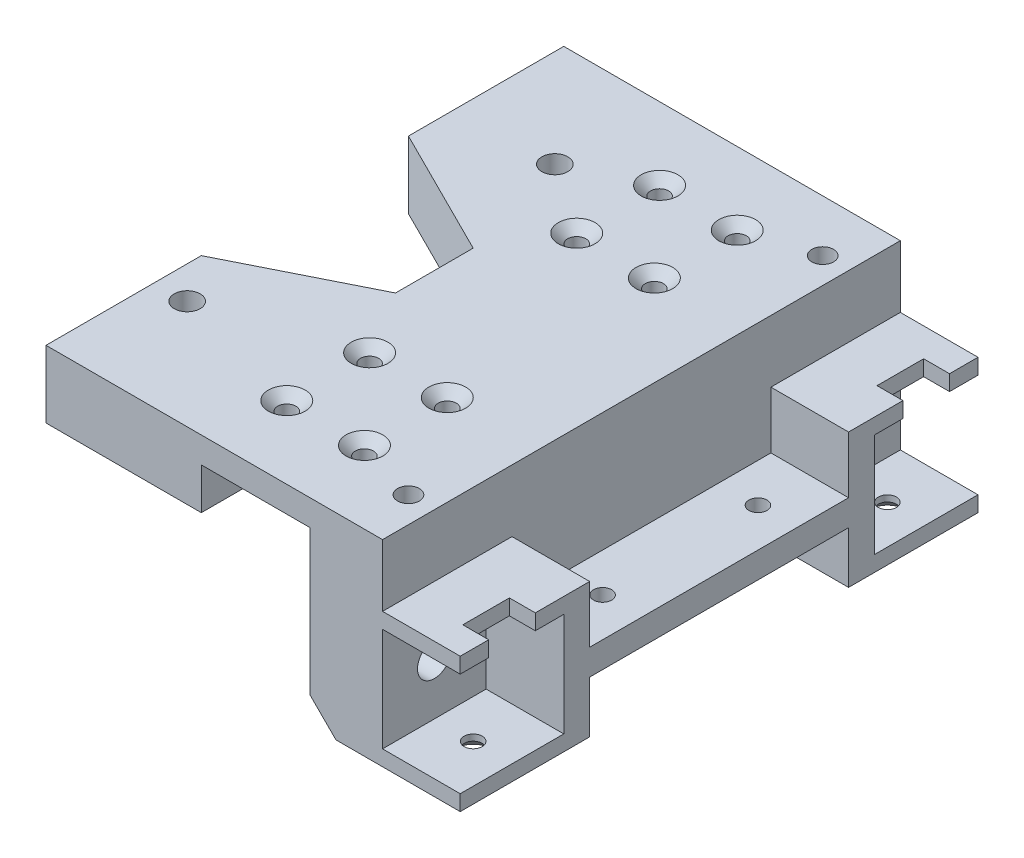
SolidWorks part; units mm, degrees
ref_plane "Front Plane" through (0, 0, 0) normal (0, 0, 1) x (1, 0, 0)
ref_plane "Top Plane" through (0, 0, 0) normal (0, 1, 0) x (1, 0, 0)
ref_plane "Right Plane" through (0, 0, 0) normal (1, 0, 0) x (0, 0, -1)
sketch "Sketch1" plane through (0, 0, 0) normal (0, 1, 0) x (1, 0, 0)
  line L0 (0, 50) -> (0, -50) construction
  line L1 (-10, 50) -> (10, 50)
  line L2 (-10, 50) -> (-10, -50)
  line L3 (-10, -50) -> (10, -50)
  line L4 (10, 50) -> (10, -50) construction
  line L5 (-10, 50) -> (10, -50) construction
  line L6 (-10, -50) -> (10, 50) construction
  line L7 (-7.5, 36) -> (7.5, 36) construction
  line L8 (-7.5, 36) -> (7.5, 20) construction
  line L9 (-10, 0) -> (10, 0) construction
  line L10 (-7.5, -36) -> (7.5, -20) construction
  line L11 (-7.5, -36) -> (7.5, -36) construction
  line L12 (-7.5, 20) -> (7.5, 20) construction
  line L13 (10, 50) -> (11, 50)
  line L14 (11, 50) -> (11, -50)
  line L15 (11, -50) -> (10, -50)
  circle A0 centre (-7.5, 36) radius 1.75
  circle A1 centre (7.5, 36) radius 1.75
  circle A2 centre (-7.5, 20) radius 1.75
  circle A3 centre (7.5, 20) radius 1.75
  circle A4 centre (7.5, -20) radius 1.75
  circle A5 centre (-7.5, -20) radius 1.75
  circle A6 centre (7.5, -36) radius 1.75
  circle A7 centre (-7.5, -36) radius 1.75
  point P0 (0, 0)
  point P16 (0, 36)
  dimension "D2" = 3.5
  dimension "D1" = 20
  dimension "D3" = 15
  dimension "D4" = 16
  dimension "D5" = 100
  dimension "D6" = 20
  dimension "D7" = 1
extrude "Boss-Extrude1" add sketch "Sketch1" along normal blind 5
sketch "Sketch2" plane through (11, 0, 0) normal (1, 0, 0) x (0, 0, -1)
  line L1 (-50, 5) -> (50, 5)
  line L2 (-50, 5) -> (-50, -33)
  line L3 (-50, -33) -> (50, -33)
  line L5 (50, 5) -> (50, -33)
  line L6 (50, 5) -> (50, 0) construction
  line L7 (-50, 5) -> (-50, 0) construction
  line L8 (-50, 5) -> (50, 5) construction
  dimension "D1" = 38
extrude "Boss-Extrude2" add sketch "Sketch2" along normal blind 14
sketch "Sketch3" plane through (25, 0, 0) normal (1, 0, 0) x (0, 0, -1)
  line L0 (0, 5) -> (0, -33) construction
  line L1 (-25, -18) -> (25, -18)
  line L2 (-25, -18) -> (-25, -23)
  line L3 (-25, -23) -> (25, -23)
  line L4 (25, -18) -> (25, -23)
  line L5 (50, 5) -> (-50, 5) construction
  line L6 (-50, -33) -> (50, -33) construction
  point P10 (0, -18)
  dimension "D1" = 5
  dimension "D2" = 50
  dimension "D3" = 10
extrude "Boss-Extrude3" add sketch "Sketch3" along normal blind 15
sketch "Sketch4" plane through (0, -18, 0) normal (0, 1, 0) x (1, 0, 0)
  line L0 (25, 0) -> (40, 0) construction
  line L1 (25, 25) -> (25, -25) construction
  line L2 (40, 25) -> (40, -25) construction
  line L3 (32.5, -15) -> (32.5, 15) construction
  circle A0 centre (32.5, 15) radius 1.75
  circle A1 centre (32.5, -15) radius 1.75
  point P8 (32.5, 0)
  dimension "D1" = 30
  dimension "D2" = 3.5
extrude "Cut-Extrude1" cut sketch "Sketch4" against normal through all
sketch "Sketch8" plane through (25, 0, 0) normal (1, 0, 0) x (0, 0, -1)
  line L0 (-50, 5) -> (-50, -33) construction
  line L1 (-50, -7) -> (-25, -7)
  line L2 (-50, -7) -> (-50, -10)
  line L3 (-50, -33) -> (-25, -33)
  line L4 (-25, -7) -> (-25, -33)
  line L5 (-50, -30) -> (-50, -33)
  line L6 (-50, -30) -> (-30, -30)
  line L8 (-50, -10) -> (-30, -10)
  line L9 (-30, -30) -> (-30, -10)
  line L10 (0, 20.9) -> (0, -20.9) construction
  line L11 (30, -30) -> (30, -10)
  line L12 (50, -10) -> (30, -10)
  line L13 (50, -30) -> (30, -30)
  line L14 (50, -30) -> (50, -33)
  line L15 (25, -7) -> (25, -33)
  line L16 (50, -33) -> (25, -33)
  line L17 (50, -7) -> (50, -10)
  line L18 (50, -7) -> (25, -7)
  line L19 (-50, -33) -> (50, -33) construction
  dimension "D1" = 3
  dimension "D2" = 5
  dimension "D3" = 3
  dimension "D4" = 20
  dimension "D5" = 20
extrude "Boss-Extrude6" add sketch "Sketch8" along normal blind 15
sketch "Sketch9" plane through (25, 0, 0) normal (1, 0, 0) x (0, 0, -1)
  line L0 (-50, -10) -> (-30, -30) construction
  line L1 (50, -10) -> (30, -30) construction
  circle A0 centre (-40, -20) radius 3.25
  circle A1 centre (40, -20) radius 3.25
  dimension "D1" = 6.5
extrude "Cut-Extrude3" cut sketch "Sketch9" against normal through all
sketch "Sketch10" plane through (11, 0, 0) normal (-1, 0, 0) x (0, 0, 1)
  circle A0 centre (-40, -20) radius 5.25
  circle A1 centre (40, -20) radius 5.25
  dimension "D1" = 10.5
extrude "Cut-Extrude4" cut sketch "Sketch10" against normal offset from surface (9 mm away) 5 up to face at (25, -20, 36.75)
sketch "Sketch11" plane through (0, -7, 0) normal (0, 1, 0) x (1, 0, 0)
  line L0 (40, -25) -> (40, -50) construction
  line L1 (40, -35.5) -> (35, -35.5)
  line L2 (40, -35.5) -> (40, -44.5)
  line L3 (40, -44.5) -> (35, -44.5)
  line L4 (35, -35.5) -> (35, -44.5)
  line L5 (35, -40) -> (40, -40) construction
  line L6 (40, -50) -> (25, -50) construction
  line L7 (-10, 0) -> (40, 0) construction
  line L8 (-10, 50) -> (-10, -50) construction
  line L9 (40, 25) -> (40, -25) construction
  line L10 (40, -35.5) -> (35, -35.5)
  line L11 (40, -44.5) -> (35, -44.5)
  line L12 (35, 40) -> (40, 40) construction
  line L13 (40, 44.5) -> (35, 44.5)
  line L14 (40, 35.5) -> (35, 35.5)
  line L15 (35, 35.5) -> (35, 44.5)
  line L16 (40, 44.5) -> (35, 44.5)
  line L17 (40, 35.5) -> (40, 44.5)
  line L18 (40, 35.5) -> (35, 35.5)
  line M7 (40, -50) -> (40, -25)
  dimension "D1" = 9
  dimension "D2" = 10
  dimension "D3" = 5
extrude "Cut-Extrude5" cut sketch "Sketch11" against normal up to next contours L1 L4 L3 M7 | L14 L17 L13 L15 region at (37.5, -7, 40) region at (37.5, -7, -40)
sketch "Sketch12" plane through (0, -30, 0) normal (0, 1, 0) x (1, 0, 0)
  line L0 (40, -40) -> (25, -40) construction
  line L1 (40, -30) -> (40, -50) construction
  line L2 (25, -25) -> (25, -50) construction
  line L3 (-20.9, 0) -> (20.9, 0) construction
  circle A0 centre (32.5, -40) radius 1.75
  circle A2 centre (32.5, 40) radius 1.75
  dimension "D1" = 3.5
extrude "Cut-Extrude6" cut sketch "Sketch12" against normal through all
sketch "Sketch13" plane through (-10, 0, 0) normal (-1, 0, 0) x (0, 0, 1)
  line L1 (-50, 5) -> (50, 5)
  line L2 (-50, 5) -> (-50, -8)
  line L3 (-50, -8) -> (50, -8)
  line L4 (50, 5) -> (50, -8)
  dimension "D1" = 13
extrude "Boss-Extrude7" add sketch "Sketch13" along normal blind 30
sketch "Sketch14" plane through (0, 5, 0) normal (0, 1, 0) x (1, 0, 0)
  line L0 (-40, -50) -> (25, -50) construction
  line L1 (-10.5, -50) -> (10.5, -50) construction
  line L2 (-10.5, -50) -> (-10.5, 50) construction
  line L3 (-10.5, 50) -> (10.5, 50) construction
  line L4 (10.5, -50) -> (10.5, 50) construction
  line L5 (25, 50) -> (-40, 50) construction
  line L6 (-27.23, 29.42) -> (-27.23, -29) construction
  line L12 (-33.73, -35.5) -> (40, -35.5) construction
  line L18 (-21.15, 35.5) -> (40, 35.5) construction
  circle A0 centre (-21.15, 29.42) radius 2.5
  circle A1 centre (-33.73, -29) radius 2.5
  circle A2 centre (-33.73, -29) radius 6.5 construction
  circle A3 centre (-21.15, 29.42) radius 6.08 construction
  point P14 (0, 50)
  dimension "D1" = 5
  dimension "D2" = 5
  dimension "D4" = 21
  dimension "D5" = 13
  dimension "D6" = 12.16
  dimension "D3" = 21.15
extrude "Cut-Extrude7" cut sketch "Sketch14" against normal through all
sketch "Sketch15" plane through (0, -8, 0) normal (0, -1, 0) x (1, 0, 0)
  line L0 (-40, -50) -> (-40, 50) construction
  line L1 (-29.73, 26.6906) -> (-29.73, 31.3094)
  line L2 (-29.73, 31.3094) -> (-33.73, 33.6188)
  line L3 (-33.73, 33.6188) -> (-37.73, 31.3094)
  line L4 (-37.73, 31.3094) -> (-37.73, 26.6906)
  line L5 (-37.73, 26.6906) -> (-33.73, 24.3812)
  line L6 (-33.73, 24.3812) -> (-29.73, 26.6906)
  line L7 (-25.15, -31.7294) -> (-21.15, -34.0388)
  line L8 (-21.15, -34.0388) -> (-17.15, -31.7294)
  line L9 (-17.15, -31.7294) -> (-17.15, -27.1106)
  line L10 (-17.15, -27.1106) -> (-21.15, -24.8012)
  line L11 (-21.15, -24.8012) -> (-25.15, -27.1106)
  line L12 (-25.15, -27.1106) -> (-25.15, -31.7294)
  circle A0 centre (-33.73, 29) radius 4 construction
  circle A1 centre (-21.15, -29.42) radius 4 construction
  dimension "D1" = 8
extrude "Cut-Extrude8" cut sketch "Sketch15" against normal blind 4
sketch "Sketch16" plane through (0, 5, 0) normal (0, 1, 0) x (1, 0, 0)
  line L0 (20, 40) -> (40, 40) construction
  line L1 (40, 50) -> (40, 30) construction
  line L2 (20, -40) -> (40, -40) construction
  line L3 (40, -30) -> (40, -50) construction
  circle A0 centre (20, 40) radius 2.1
  circle A1 centre (20, -40) radius 2.1
  dimension "D1" = 4.2
  dimension "D2" = 4.2
  dimension "D3" = 20
extrude "Cut-Extrude9" cut sketch "Sketch16" against normal blind 4
chamfer "Chamfer1" distance 1.8 angle 45 8 edges at (-7.5, 5, -34.25) (7.5, 5, -34.25) (-7.5, 5, -18.25) (7.5, 5, -18.25) (-7.5, 5, 18.25) (7.5, 5, 18.25) (-7.5, 5, 34.25) (7.5, 5, 34.25)
sketch "Sketch17" plane through (0, 5, 0) normal (0, 1, 0) x (1, 0, 0)
  line L0 (-40, 20) -> (-15, 7.5)
  line L1 (-40, -50) -> (-40, 50) construction
  line L2 (-15, 7.5) -> (-15, -7.5)
  line L3 (-15, -7.5) -> (-40, -20)
  line L4 (-40, -20) -> (-40, 20)
  point P6 (-15, 0)
  dimension "D1" = 15
  dimension "D2" = 40
  dimension "D3" = 15
extrude "Cut-Extrude10" cut sketch "Sketch17" against normal through all
chamfer "Chamfer2" distance 1.8 angle 45 2 edges at (32.5, -33, -41.75) (32.5, -33, 41.75)
chamfer "Chamfer3" distance 5 angle 45 1 edges at (11, -33, 0)
